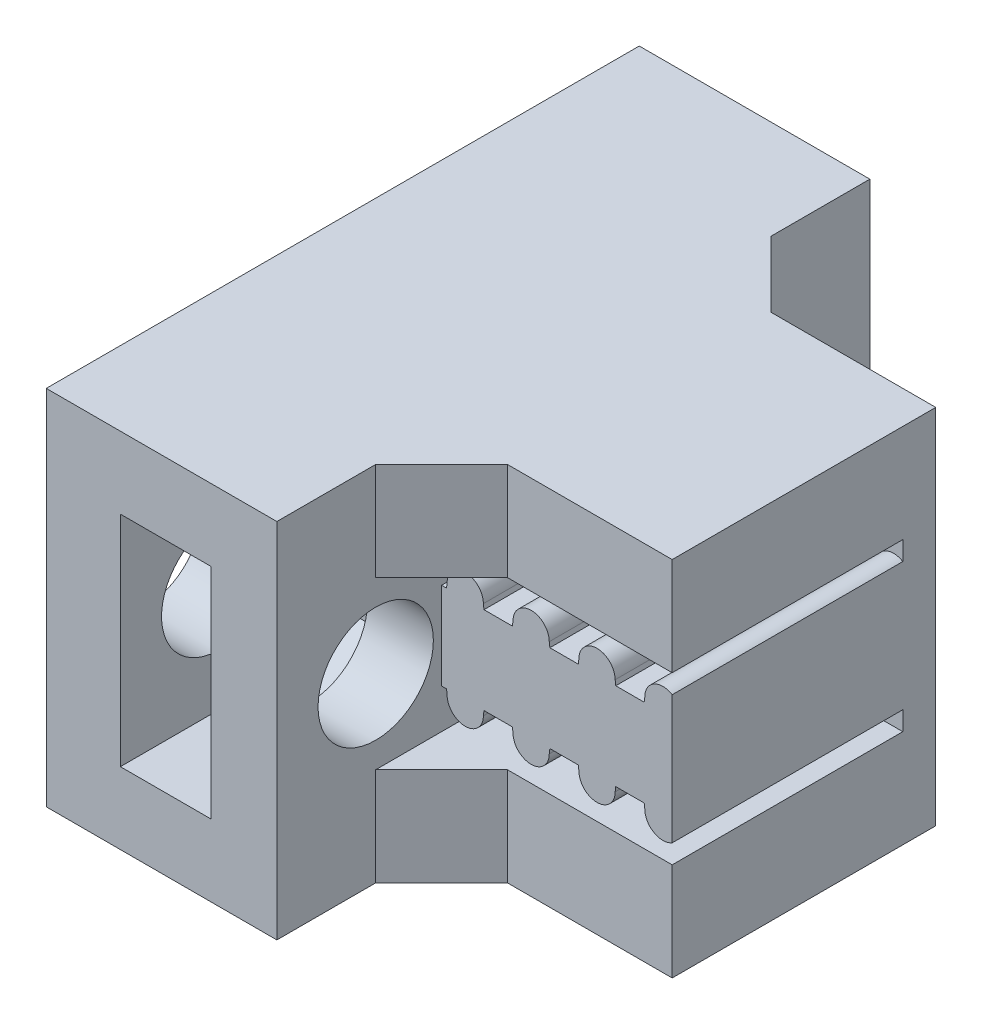
SolidWorks part; units mm, degrees
ref_plane "Спереди" through (0, 0, 0) normal (0, 0, 1) x (1, 0, 0)
ref_plane "Сверху" through (0, 0, 0) normal (0, 1, 0) x (1, 0, 0)
ref_plane "Справа" through (0, 0, 0) normal (1, 0, 0) x (0, 0, -1)
sketch "Эскиз1" plane through (0, 0, 0) normal (0, 0, 1) x (1, 0, 0)
  line L1 (-3.5, -5.5) -> (3.5, -5.5)
  line L2 (-3.5, -5.5) -> (-3.5, 5.5)
  line L3 (-3.5, 5.5) -> (3.5, 5.5)
  line L4 (3.5, -5.5) -> (3.5, 5.5)
  line L5 (-3.5, -5.5) -> (3.5, 5.5) construction
  line L6 (-3.5, 5.5) -> (3.5, -5.5) construction
  point P0 (0, 0)
  dimension "D1" = 11
  dimension "D2" = 7
extrude "Бобышка-Вытянуть1" add sketch "Эскиз1" along normal blind 8
sketch "Эскиз2" plane through (0, 0, 8) normal (0, 0, 1) x (1, 0, 0)
  line L0 (-3.5, 5.5) -> (-3.5, -5.5) construction
  line L1 (-3.5, 0.625) -> (3.5, 0.625) construction
  line L2 (-3.5, 0.625) -> (-3.5, -0.625) construction
  line L3 (-3.5, -0.625) -> (3.5, -0.625) construction
  line L4 (3.5, 0.625) -> (3.5, -0.625) construction
  line L5 (3.5, -5.5) -> (3.5, 5.5) construction
  line L6 (-2.7816, 2.025) -> (-2.7816, 1.475) construction
  line L7 (-3.5, 0.625) -> (3.5, 0.625)
  line L8 (-3.5, 0.625) -> (-3.5, 2.525)
  line L9 (-3.5, 2.525) -> (3.5, 2.525)
  line L10 (3.5, 0.625) -> (3.5, 2.525)
  line L11 (-3.5, 0.625) -> (3.5, 0.625)
  line L12 (-3.5, 0.625) -> (-3.5, 1.325)
  line L13 (-3.5, 1.325) -> (3.5, 1.325)
  line L14 (3.5, 0.625) -> (3.5, 1.325)
  line L15 (-3.3316, 1.475) -> (-3.35, 1.325)
  line L16 (-2.2316, 1.475) -> (-2.2132, 1.325)
  line L17 (-1.3316, 1.475) -> (-1.35, 1.325)
  line L18 (-0.2316, 1.475) -> (-0.2132, 1.325)
  line L19 (-0.7816, 2.025) -> (-0.7816, 1.475) construction
  line L20 (0.6684, 1.475) -> (0.65, 1.325)
  line L21 (1.7684, 1.475) -> (1.7868, 1.325)
  line L22 (1.2184, 2.025) -> (1.2184, 1.475) construction
  line L23 (2.6684, 1.475) -> (2.65, 1.325)
  line L24 (3.7684, 1.475) -> (3.7868, 1.325)
  line L25 (3.2184, 2.025) -> (3.2184, 1.475) construction
  line L26 (3.85, 0) -> (-3.85, 0) construction
  line L27 (3.2184, -2.025) -> (3.2184, -1.475) construction
  line L28 (1.2184, -2.025) -> (1.2184, -1.475) construction
  line L29 (-0.7816, -2.025) -> (-0.7816, -1.475) construction
  line L30 (-2.7816, -2.025) -> (-2.7816, -1.475) construction
  line L31 (-3.5, -0.625) -> (3.5, -0.625) construction
  line L32 (3.7684, -1.475) -> (3.7868, -1.325)
  line L33 (2.6684, -1.475) -> (2.65, -1.325)
  line L34 (1.7684, -1.475) -> (1.7868, -1.325)
  line L35 (0.6684, -1.475) -> (0.65, -1.325)
  line L36 (-0.2316, -1.475) -> (-0.2132, -1.325)
  line L37 (-1.3316, -1.475) -> (-1.35, -1.325)
  line L38 (-2.2316, -1.475) -> (-2.2132, -1.325)
  line L39 (-3.3316, -1.475) -> (-3.35, -1.325)
  line L40 (3.5, -0.625) -> (3.5, -1.325)
  line L41 (-3.5, -1.325) -> (3.5, -1.325)
  line L42 (-3.5, -0.625) -> (-3.5, -1.325)
  line L43 (-3.5, -0.625) -> (3.5, -0.625)
  line L44 (3.5, -0.625) -> (3.5, -2.525)
  line L45 (-3.5, -2.525) -> (3.5, -2.525)
  line L46 (-3.5, -0.625) -> (-3.5, -2.525)
  line L47 (-3.5, -0.625) -> (3.5, -0.625)
  circle A0 centre (-2.7816, 1.475) radius 0.55
  circle A1 centre (-0.7816, 1.475) radius 0.55
  circle A2 centre (1.2184, 1.475) radius 0.55
  circle A3 centre (3.2184, 1.475) radius 0.55
  circle A4 centre (3.2184, -1.475) radius 0.55
  circle A5 centre (1.2184, -1.475) radius 0.55
  circle A6 centre (-0.7816, -1.475) radius 0.55
  circle A7 centre (-2.7816, -1.475) radius 0.55
  point P8 (3.5, 0)
  point P17 (-2.7816, 2.025)
  point P26 (-0.7816, 2.025)
  point P34 (1.2184, 2.025)
  point P42 (3.2184, 2.025)
  point P80 (3.2184, -2.025)
  point P81 (1.2184, -2.025)
  point P82 (-0.7816, -2.025)
  point P83 (-2.7816, -2.025)
  line M8 (3.5, -5.5) -> (3.5, 5.5)
  line M10 (-3.5, 5.5) -> (-3.5, -5.5)
  dimension "D4" = 1.1
  dimension "D5" = 7
  dimension "D1" = 1.25
  dimension "D2" = 1.9
  dimension "D3" = 0.7
  dimension "D6" = 1.4
  dimension "D7" = 0.15
  dimension "D8" = 4
extrude "Вырез-Вытянуть1" cut sketch "Эскиз2" against normal offset from surface (7 mm away) 1 contours A3 L9 L13 L15 A0 L16 L17 A1 L18 L20 A2 L21 L23 M8 M10 | L38 A7 L39 L41 L45 A4 L33 L34 A5 L35 L36 A6 L37 M10 M8 region at (-0.0144, 2.0456, 8) region at (-0.0144, -2.0456, 8) up to face at (0, 0, 0)
sketch "Эскиз3" plane through (-3.5, 0, 0) normal (-1, 0, 0) x (0, 0, 1)
  line L1 (-5, 5.5) -> (13, 5.5)
  line L2 (-5, 5.5) -> (-5, -5.5)
  line L3 (-5, -5.5) -> (13, -5.5)
  line L4 (13, 5.5) -> (13, -5.5)
  line L5 (8, 5.5) -> (0, 5.5) construction
  line L6 (8, -5.5) -> (0, -5.5) construction
  line L7 (-2, 0) -> (10, 0) construction
  circle A0 centre (10, 0) radius 1.75
  circle A1 centre (-2, 0) radius 1.75
  point P4 (4, 5.5)
  point P13 (4, 0)
  point P14 (4, -5.5)
  dimension "D3" = 3.5
  dimension "D1" = 18
  dimension "D2" = 12
extrude "Бобышка-Вытянуть2" add sketch "Эскиз3" along normal blind 7
sketch "Эскиз5" plane through (-3.5, 0, 0) normal (1, 0, 0) x (0, 0, -1)
  line L0 (-13, -5.5) -> (-13, 5.5) construction
  line L1 (-10, 3.3198) -> (-12.875, 1.6599)
  line L2 (-12.875, 1.6599) -> (-12.875, -1.6599)
  line L3 (-12.875, -1.6599) -> (-10, -3.3198)
  line L4 (-10, -3.3198) -> (-7.125, -1.6599)
  line L5 (-7.125, -1.6599) -> (-7.125, 1.6599)
  line L6 (-7.125, 1.6599) -> (-10, 3.3198)
  line L7 (-8, 5.5) -> (0, 5.5) construction
  line L8 (-4, 5.5) -> (-4, -5.4755) construction
  line L9 (-0.875, 1.6599) -> (2, 3.3198)
  line L10 (-0.875, -1.6599) -> (-0.875, 1.6599)
  line L11 (2, -3.3198) -> (-0.875, -1.6599)
  line L12 (4.875, -1.6599) -> (2, -3.3198)
  line L13 (4.875, 1.6599) -> (4.875, -1.6599)
  line L14 (2, 3.3198) -> (4.875, 1.6599)
  line L15 (-10, 3.3198) -> (-13, 3.3198)
  line L16 (-10, -3.3198) -> (-13, -3.3198)
  line L17 (2, 3.3198) -> (5, 3.3198)
  line L18 (5, 5.5) -> (5, -5.5) construction
  line L19 (2, -3.3198) -> (5, -3.3198)
  line L20 (-13, 3.3198) -> (-13, -3.3198)
  line L21 (5, 3.3198) -> (5, -3.3198)
  circle A0 centre (-10, 0) radius 2.875 construction
  circle A1 centre (2, 0) radius 2.875 construction
  point P15 (-4, 5.5)
  line M5 (-13, 5.5) -> (-13, -5.5)
  line M10 (-1, -1.325) -> (-8, -1.325)
  line M11 (-8, -1.325) -> (-8, 1.325)
  line M12 (-8, 1.325) -> (-1, 1.325)
  circle M15 centre (-10, 0) radius 1.75
  dimension "D1" = 5.75
extrude "Вырез-Вытянуть3" cut sketch "Эскиз5" against normal blind 2.75 from offset 2 contours L14 L9 L10 L11 L12 L13 | L21 L17 L14 L13 L12 L19 | L5 M10 M12 M11 | L5 L6 L1 L2 L3 L4 M10 M11 M12 M15 | L16 L3 L2 L1 L15 M5 region at (-3.5, 2.4138, 8.6064) region at (-3.5, 2.5529, 11.4739) region at (-3.5, 0, 7.5625) region at (-3.5, 0, -2) region at (-3.5, 3.2469, -3.5) offset against normal yes
chamfer "Фаска1" distance 2 angle 45 3 edges at (-3.5, 0, 0) (-3.5, 4.0125, 8) (-3.5, -4.0125, 8)
